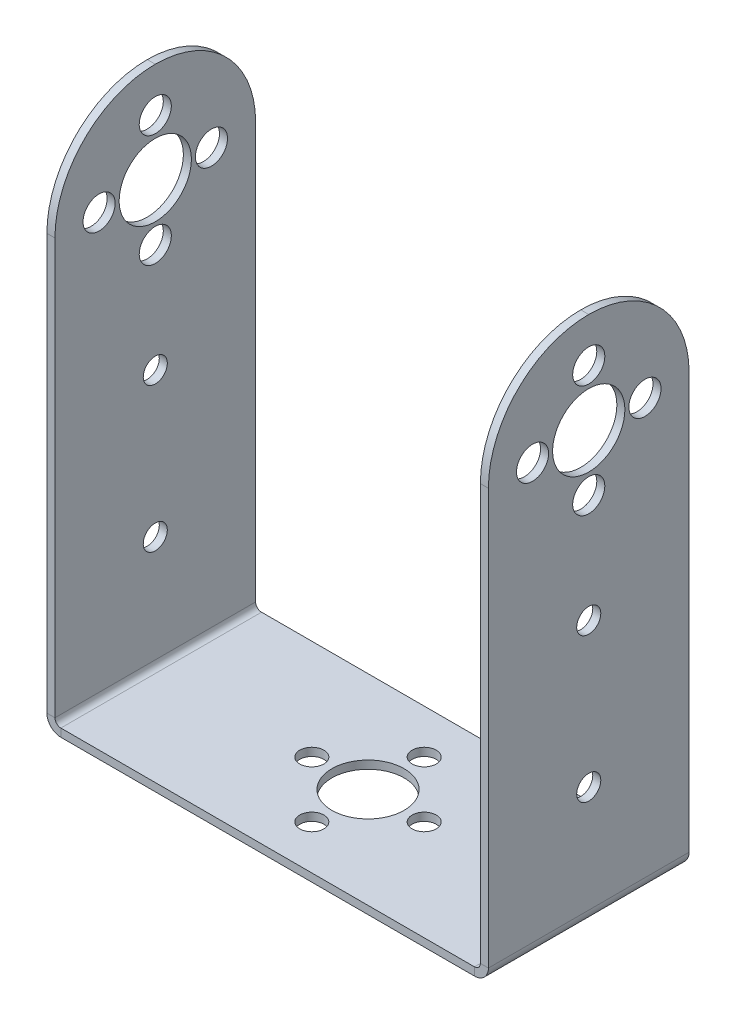
SolidWorks part; units mm, degrees
note: The reader was unsure of these and kept them because the rebuilt part matched: thickness of "Base-Flange1", "Edge-Flange1", "Sheet-Metal1", "Sheet-Metal2", "Sheet-Metal3"; flange length of "Edge-Flange1".
ref_plane "Front Plane" through (0, 0, 0) normal (0, 0, 1) x (1, 0, 0)
ref_plane "Top Plane" through (0, 0, 0) normal (0, 1, 0) x (1, 0, 0)
ref_plane "Right Plane" through (0, 0, 0) normal (1, 0, 0) x (0, 0, -1)
sketch "Sketch1" plane through (0, 0, 0) normal (0, 1, 0) x (1, 0, 0)
  line L0 (-7, 0) -> (7, 0) construction
  line L1 (26.5, 12.5) -> (-26.5, 12.5)
  line L2 (26.5, 12.5) -> (26.5, -12.5)
  line L3 (26.5, -12.5) -> (-26.5, -12.5)
  line L4 (-26.5, 12.5) -> (-26.5, -12.5)
  line L5 (26.5, 12.5) -> (-26.5, -12.5) construction
  line L6 (26.5, -12.5) -> (-26.5, 12.5) construction
  line L7 (0, 12.5) -> (0, -12.5) construction
  circle A0 centre (0, 0) radius 4.5
  circle A1 centre (-7, 0) radius 1.5
  circle A2 centre (7, 0) radius 1.5
  circle A3 centre (0, 7) radius 1.5
  circle A4 centre (0, -7) radius 1.5
  point P0 (0, 0)
  dimension "D3" = 9
  dimension "D4" = 3
  dimension "D6" = 7
  dimension "D1" = 53
  dimension "D2" = 25
  dimension "D5" = 7
  dimension "D7" = 7
base flange "Base-Flange1" sketch "Sketch1" thickness 1 reverse thickness direction yes parameters "D1"=0.7366
edge flange "Edge-Flange1" sketch "Sketch10" flange profiles "Sketch10", "Sketch11" flange angle 90 flange length 65 flange position material outside bend radius 0.7366 thickness 1 relief rectangular parameters "D6"=10, "D8"=1
sketch "Sketch10" plane through (-26.5, 1, 0) normal (-1, 0, 0) x (0, 0, 1)
  line L2 (-12.5, 0) -> (-12.5, 65)
  line L3 (-12.5, 65) -> (12.5, 65)
  line L4 (12.5, 65) -> (12.5, 0)
  line L7 (-12.5, 0) -> (12.5, 0) construction
  line L8 (-12.5, 0) -> (12.5, 0)
sketch "Sketch11" plane through (26.5, 1, 0) normal (1, 0, 0) x (0, 0, -1)
  line L2 (-12.5, 0) -> (-12.5, 65)
  line L3 (-12.5, 65) -> (12.5, 65)
  line L4 (12.5, 65) -> (12.5, 0)
  line L7 (-12.5, 0) -> (12.5, 0) construction
  line L8 (-12.5, 0) -> (12.5, 0)
bend "EdgeBend1" bend radius 0.7366 bend angle 90 parameters "D5"=1
bend "EdgeBend2" bend radius 0.7366 bend angle 90 parameters "D5"=2
sketch "Sketch13" plane through (0, 0, 0) normal (1, 0, 0) x (0, 0, -1)
  line L0 (12.5, 66) -> (-12.5, 66) construction
  line L1 (0, 63.4781) -> (0, 0) construction
  line L2 (12.5, 0) -> (-12.5, 0) construction
  circle A4 centre (0, 53.5) radius 4.5
  circle A5 centre (-7, 53.5) radius 2
  circle A6 centre (7, 53.5) radius 2
  circle A7 centre (0, 46.5) radius 2
  circle A8 centre (0, 60.5) radius 2
  circle A9 centre (0, 33) radius 1.5
  circle A10 centre (0, 15) radius 1.5
  dimension "D1" = 9
  dimension "D4" = 7
  dimension "D2" = 4
  dimension "D8" = 3
  dimension "D9" = 3
  dimension "D3" = 7
  dimension "D5" = 7
  dimension "D6" = 7
  dimension "D7" = 5.5
  dimension "D10" = 15
  dimension "D11" = 33
extrude "Cut-Extrude1" cut sketch "Sketch13" against normal through all both and the other way through all normal cut yes
fillet "Fillet1" radius 12.5 4 edges at (-27, 66, -12.5) (-27, 66, 12.5) (27, 66, -12.5) (27, 66, 12.5)
sketch "Bend-Lines1" [suppressed] plane through (0, 0, 0) normal (0, 1, 0) x (1, 0, 0)
sketch "Bounding-Box1" [suppressed] plane through (0, 0, 0) normal (0, 1, 0) x (1, 0, 0)
sheet metal parameters "Sheet-Metal1" thickness 1 parameters "D1"=0.7366
flat pattern "Flat-Pattern1" [suppressed]
sketch "Bend-Lines2" plane through (0, 0, 0) normal (0, 1, 0) x (1, 0, 0)
sketch3d "Bounding-Box2" [suppressed]
  line L0 (12, 5, 0) -> (-12, 5, 0) construction
  line L1 (12, -5, 0) -> (-12, -5, 0) construction
  line L2 (12, 5, 0) -> (12, -5, 0) construction
  line L3 (-12, 5, 0) -> (-12, -5, 0) construction
sheet metal parameters "Sheet-Metal2" thickness 1 parameters "D1"=0.7366, "D7"=2
flat pattern "Flat-Pattern1"
sketch "Bend-Lines2" plane through (0, 0, 0) normal (0, -1, 0) x (-1, 0, 0)
  line L0 (-12.6273, 5) -> (-12.6273, -5) construction
  line L1 (12.6273, -5) -> (12.6273, 5) construction
  line L2 (-12.6273, 5) -> (-12.6273, -5) construction
  line L3 (12.6273, -5) -> (12.6273, 5) construction
sketch3d "Bounding-Box2" [suppressed]
  line L0 (-53.2546, 5, 0) -> (53.2546, 5, 0) construction
  line L1 (-53.2546, -5, 0) -> (53.2546, -5, 0) construction
  line L2 (-53.2546, 5, 0) -> (-53.2546, -5, 0) construction
  line L3 (53.2546, 5, 0) -> (53.2546, -5, 0) construction
bend of the flat pattern "Flatten-<EdgeBend1>1"
bend of the flat pattern "Flatten-<EdgeBend2>1"
sheet metal parameters "Sheet-Metal3" thickness 1 parameters "D1"=0.7366, "D7"=2
flat pattern "Flat-Pattern1"
sketch "Bend-Lines2" plane through (0, 0, 0) normal (0, -1, 0) x (-1, 0, 0)
  line L0 (-26.7346, 12.5) -> (-26.7346, -12.5) construction
  line L1 (26.7346, -12.5) -> (26.7346, 12.5) construction
  line L2 (-26.7346, 12.5) -> (-26.7346, -12.5) construction
  line L3 (26.7346, -12.5) -> (26.7346, 12.5) construction
sketch3d "Bounding-Box2" [suppressed]
  line L0 (-91.9692, 12.5, 0) -> (91.9692, 12.5, 0) construction
  line L1 (-91.9692, -12.5, 0) -> (91.9692, -12.5, 0) construction
  line L2 (-91.9692, 12.5, 0) -> (-91.9692, -12.5, 0) construction
  line L3 (91.9692, 12.5, 0) -> (91.9692, -12.5, 0) construction
bend of the flat pattern "Flatten-<EdgeBend1>1"
bend of the flat pattern "Flatten-<EdgeBend2>1"
